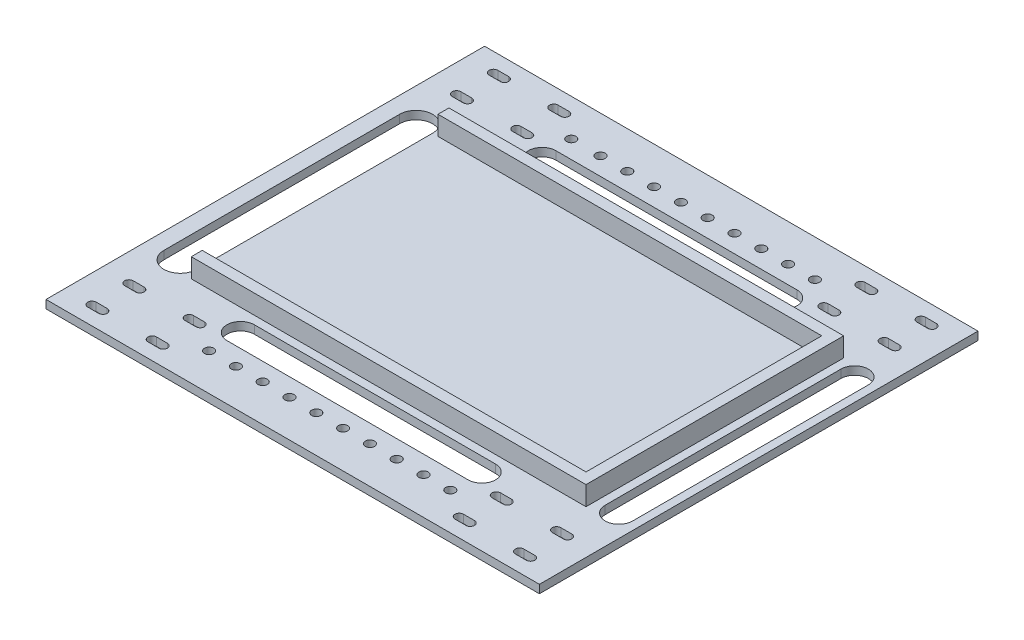
SolidWorks part; units mm, degrees
note: The reader was unsure of these and kept them because the rebuilt part matched: shared geometry of "Sketch1<3>".
ref_plane "Front Plane" through (0, 0, 0) normal (0, 0, 1) x (1, 0, 0)
ref_plane "Top Plane" through (0, 0, 0) normal (0, 1, 0) x (1, 0, 0)
ref_plane "Right Plane" through (0, 0, 0) normal (1, 0, 0) x (0, 0, -1)
sketch "Sketch1" plane through (0, 0, 0) normal (0, 1, 0) x (1, 0, 0)
  line L0 (0, -45) -> (0, 45) construction
  line L1 (-90, -80) -> (90, -80)
  line L2 (-90, -80) -> (-90, 80)
  line L3 (-90, 80) -> (90, 80)
  line L4 (90, -80) -> (90, 80)
  line L5 (-90, -80) -> (90, 80) construction
  line L6 (-90, 80) -> (90, -80) construction
  line L17 (-70, 43) -> (70, 43)
  line L18 (-70, 43) -> (-70, 47)
  line L21 (-70, 47) -> (70, 47)
  line L22 (70, 43) -> (70, 47)
  line L23 (-70, 43) -> (70, 47) construction
  line L24 (-70, 47) -> (70, 43) construction
  line L25 (-70, -47) -> (70, -47)
  line L26 (-70, -47) -> (-70, -43)
  line L27 (-70, -43) -> (70, -43)
  line L28 (70, -47) -> (70, -43)
  line L29 (-70, -47) -> (70, -43) construction
  line L30 (-70, -43) -> (70, -47) construction
  line L31 (0, 0) -> (-90, 0) construction
  line L36 (74, -47) -> (70, -47)
  line L37 (74, -47) -> (74, 47)
  line L38 (74, 47) -> (70, 47)
  line L39 (70, -47) -> (70, 47)
  line L40 (74, -47) -> (70, 47) construction
  line L41 (74, 47) -> (70, -47) construction
  line L42 (-80, -59.75) -> (-76, -59.75) construction
  line L43 (-80, -58.195) -> (-76, -58.195)
  line L44 (-80, -61.305) -> (-76, -61.305)
  line L45 (-58, -59.75) -> (-54, -59.75) construction
  line L46 (-58, -58.195) -> (-54, -58.195)
  line L47 (-58, -61.305) -> (-54, -61.305)
  line L48 (-80, -73.25) -> (-76, -73.25) construction
  line L49 (-80, -71.695) -> (-76, -71.695)
  line L50 (-80, -74.805) -> (-76, -74.805)
  line L51 (-58, -73.25) -> (-54, -73.25) construction
  line L52 (-58, -71.695) -> (-54, -71.695)
  line L53 (-58, -74.805) -> (-54, -74.805)
  line L54 (-80, 73.25) -> (-76, 73.25) construction
  line L55 (-80, 71.695) -> (-76, 71.695)
  line L56 (-80, 74.805) -> (-76, 74.805)
  line L57 (-58, 73.25) -> (-54, 73.25) construction
  line L58 (-58, 71.695) -> (-54, 71.695)
  line L59 (-58, 74.805) -> (-54, 74.805)
  line L60 (-58, 59.75) -> (-54, 59.75) construction
  line L61 (-58, 58.195) -> (-54, 58.195)
  line L62 (-58, 61.305) -> (-54, 61.305)
  line L63 (-80, 59.75) -> (-76, 59.75) construction
  line L64 (-80, 58.195) -> (-76, 58.195)
  line L65 (-80, 61.305) -> (-76, 61.305)
  line L66 (80, -73.25) -> (76, -73.25) construction
  line L67 (80, -71.695) -> (76, -71.695)
  line L68 (80, -74.805) -> (76, -74.805)
  line L69 (80, -59.75) -> (76, -59.75) construction
  line L70 (80, -58.195) -> (76, -58.195)
  line L71 (80, -61.305) -> (76, -61.305)
  line L72 (58, -59.75) -> (54, -59.75) construction
  line L73 (58, -58.195) -> (54, -58.195)
  line L74 (58, -61.305) -> (54, -61.305)
  line L75 (58, -73.25) -> (54, -73.25) construction
  line L76 (58, -71.695) -> (54, -71.695)
  line L77 (58, -74.805) -> (54, -74.805)
  line L78 (80, 59.75) -> (76, 59.75) construction
  line L79 (80, 58.195) -> (76, 58.195)
  line L80 (80, 61.305) -> (76, 61.305)
  line L81 (58, 59.75) -> (54, 59.75) construction
  line L82 (58, 58.195) -> (54, 58.195)
  line L83 (58, 61.305) -> (54, 61.305)
  line L84 (58, 73.25) -> (54, 73.25) construction
  line L85 (58, 71.695) -> (54, 71.695)
  line L86 (58, 74.805) -> (54, 74.805)
  line L87 (80, 73.25) -> (76, 73.25) construction
  line L88 (80, 71.695) -> (76, 71.695)
  line L89 (80, 74.805) -> (76, 74.805)
  line L90 (-56, 66.5) -> (56, 66.5) construction
  line L91 (-56, 73.25) -> (-56, 59.75) construction
  line L92 (56, 73.25) -> (56, 59.75) construction
  line L93 (-56, -66.5) -> (56, -66.5) construction
  line L94 (56, -73.25) -> (56, -59.75) construction
  line L95 (-56, -73.25) -> (-56, -59.75) construction
  line L96 (-78, 43) -> (-78, -43) construction
  line L97 (-78, -43) -> (-78, 43) construction
  line L98 (-84, -43) -> (-84, 43)
  line L99 (-72, -43) -> (-72, 43)
  line L100 (82, -43) -> (82, 43) construction
  line L101 (77, -43) -> (77, 43)
  line L102 (87, -43) -> (87, 43)
  line L103 (-44, 55) -> (44, 55) construction
  line L104 (-44, 60) -> (44, 60)
  line L105 (-44, 50) -> (44, 50)
  line L106 (-44, -55) -> (44, -55) construction
  line L107 (-44, -60) -> (44, -60)
  line L108 (-44, -50) -> (44, -50)
  arc A0 (-80, -58.195) -> (-80, -61.305) centre (-80, -59.75) ccw
  arc A1 (-76, -61.305) -> (-76, -58.195) centre (-76, -59.75) ccw
  arc A2 (-58, -58.195) -> (-58, -61.305) centre (-58, -59.75) ccw
  arc A3 (-54, -61.305) -> (-54, -58.195) centre (-54, -59.75) ccw
  arc A4 (-80, -71.695) -> (-80, -74.805) centre (-80, -73.25) ccw
  arc A5 (-76, -74.805) -> (-76, -71.695) centre (-76, -73.25) ccw
  arc A6 (-58, -71.695) -> (-58, -74.805) centre (-58, -73.25) ccw
  arc A7 (-54, -74.805) -> (-54, -71.695) centre (-54, -73.25) ccw
  arc A8 (-80, 71.695) -> (-80, 74.805) centre (-80, 73.25) cw
  arc A9 (-76, 74.805) -> (-76, 71.695) centre (-76, 73.25) cw
  arc A10 (-58, 71.695) -> (-58, 74.805) centre (-58, 73.25) cw
  arc A11 (-54, 74.805) -> (-54, 71.695) centre (-54, 73.25) cw
  arc A12 (-58, 58.195) -> (-58, 61.305) centre (-58, 59.75) cw
  arc A13 (-54, 61.305) -> (-54, 58.195) centre (-54, 59.75) cw
  arc A14 (-80, 58.195) -> (-80, 61.305) centre (-80, 59.75) cw
  arc A15 (-76, 61.305) -> (-76, 58.195) centre (-76, 59.75) cw
  arc A16 (80, -71.695) -> (80, -74.805) centre (80, -73.25) cw
  arc A17 (76, -74.805) -> (76, -71.695) centre (76, -73.25) cw
  arc A18 (80, -58.195) -> (80, -61.305) centre (80, -59.75) cw
  arc A19 (76, -61.305) -> (76, -58.195) centre (76, -59.75) cw
  arc A20 (58, -58.195) -> (58, -61.305) centre (58, -59.75) cw
  arc A21 (54, -61.305) -> (54, -58.195) centre (54, -59.75) cw
  arc A22 (58, -71.695) -> (58, -74.805) centre (58, -73.25) cw
  arc A23 (54, -74.805) -> (54, -71.695) centre (54, -73.25) cw
  arc A24 (80, 58.195) -> (80, 61.305) centre (80, 59.75) ccw
  arc A25 (76, 61.305) -> (76, 58.195) centre (76, 59.75) ccw
  arc A26 (58, 58.195) -> (58, 61.305) centre (58, 59.75) ccw
  arc A27 (54, 61.305) -> (54, 58.195) centre (54, 59.75) ccw
  arc A28 (58, 71.695) -> (58, 74.805) centre (58, 73.25) ccw
  arc A29 (54, 74.805) -> (54, 71.695) centre (54, 73.25) ccw
  arc A30 (80, 71.695) -> (80, 74.805) centre (80, 73.25) ccw
  arc A31 (76, 74.805) -> (76, 71.695) centre (76, 73.25) ccw
  arc A32 (-84, -43) -> (-72, -43) centre (-78, -43) ccw
  arc A33 (-72, 43) -> (-84, 43) centre (-78, 43) ccw
  arc A34 (77, -43) -> (87, -43) centre (82, -43) ccw
  arc A35 (87, 43) -> (77, 43) centre (82, 43) ccw
  arc A36 (-44, 60) -> (-44, 50) centre (-44, 55) ccw
  arc A37 (44, 50) -> (44, 60) centre (44, 55) ccw
  arc A38 (-44, -60) -> (-44, -50) centre (-44, -55) cw
  arc A39 (44, -50) -> (44, -60) centre (44, -55) cw
  point P0 (0, 0)
  point P6 (0, 45)
  point P7 (0, -45)
  point P19 (0, 0)
  point P21 (72, 0)
  point P27 (-78, -59.75)
  point P33 (-56, -59.75)
  point P40 (-78, -73.25)
  point P47 (-56, -73.25)
  point P56 (0, 66.5)
  point P59 (-78, 73.25)
  point P66 (-56, 73.25)
  point P73 (-56, 59.75)
  point P80 (-78, 59.75)
  point P87 (78, -73.25)
  point P94 (78, -59.75)
  point P101 (56, -59.75)
  point P108 (56, -73.25)
  point P115 (78, 59.75)
  point P122 (56, 59.75)
  point P129 (56, 73.25)
  point P136 (78, 73.25)
  point P142 (-44, 66.5)
  point P143 (-56, 66.5)
  point P144 (-34.2222, 66.5)
  point P148 (-24.4444, 66.5)
  point P149 (-14.6667, 66.5)
  point P150 (-4.8889, 66.5)
  point P151 (4.8889, 66.5)
  point P152 (14.6667, 66.5)
  point P153 (24.4444, 66.5)
  point P154 (34.2222, 66.5)
  point P155 (44, 66.5)
  point P157 (-4.8889, -66.5)
  point P158 (4.8889, -66.5)
  point P159 (14.6667, -66.5)
  point P160 (24.4444, -66.5)
  point P161 (34.2222, -66.5)
  point P162 (44, -66.5)
  point P167 (-14.6667, -66.5)
  point P168 (-24.4444, -66.5)
  point P169 (-34.2222, -66.5)
  point P170 (-44, -66.5)
  point P174 (-78, 0)
  point P181 (82, 0)
  point P187 (0, 55)
  point P193 (0, 0)
  point P194 (0, 0)
  point P195 (0, 0)
  point P196 (0, 58.195)
  point P197 (0, 0)
  point P200 (0, -55)
  dimension "D1" = 180
  dimension "D2" = 3.11
  dimension "D3" = 86
  dimension "D4" = 4
  dimension "D5" = 140
  dimension "D6" = 4
  dimension "D7" = 18
  dimension "D8" = 13.5
  dimension "D9" = 6.75
  dimension "D10" = 10
  dimension "D11" = 160
  dimension "D12" = 12
  dimension "D14" = 12
  dimension "D15" = 10
  dimension "D16" = 8
  dimension "D17" = 8
  dimension "D18" = 10
  dimension "D13" = 10
extrude "Boss-Extrude1" add sketch "Sketch1" along normal blind 3 contours L27 L39 L17 L18 L3 L2 L1 L26 | L17 L22 L3 L18 | L39 L28 L1 L37 L3 L22 | L37 L1 L4 L3
extrude "Boss-Extrude2" add sketch "Sketch1<3>" along normal blind 10 contours L39 L28 L1 L37 L3 L22
sketch "Sketch1<3>" plane through (0, 0, 0) normal (0, 1, 0) x (1, 0, 0) same geometry as "Sketch1"
hole_wizard "M3 Clearance Hole1" positions "Sketch2" profile "Sketch3" hole size "M3" standard "ANSI Metric"
sketch "Sketch2" plane through (0, 3, 0) normal (0, 1, 0) x (1, 0, 0)
  line L0 (-56, 66.5) -> (56, 66.5) construction
  point P0 (-44, -66.5)
  point P3 (-34.2222, -66.5)
  point P6 (-24.4444, -66.5)
  point P9 (-14.6667, -66.5)
  point P12 (-4.8889, -66.5)
  point P15 (4.8889, -66.5)
  point P18 (14.6667, -66.5)
  point P21 (24.4444, -66.5)
  point P24 (34.2222, -66.5)
  point P27 (44, -66.5)
  point P30 (44, 66.5)
  point P33 (34.2222, 66.5)
  point P36 (24.4444, 66.5)
  point P39 (14.6667, 66.5)
  point P42 (4.8889, 66.5)
  point P45 (-4.8889, 66.5)
  point P48 (-14.6667, 66.5)
  point P51 (-24.4444, 66.5)
  point P54 (-34.2222, 66.5)
  point P57 (-44.8813, 66.5)
sketch "Sketch3" plane through (-44, 3, 66.5) normal (1, 0, 0) x (0, 0, 1)
  line L0 (0, 0) -> (0, 4.0205)
  line L1 (0, 4.0205) -> (1.7, 2.999)
  line L2 (1.7, 2.999) -> (1.7, 0)
  line L5 (1.7, 0) -> (0, 0)
  line L10 (0, 4.0205) -> (-1.7, 2.999) construction
  line L11 (0, -6.35) -> (0, 107.95) construction
  dimension "Hole Dia." = 3.4
  dimension "Hole Depth" = 2.999
  dimension "Drill Angle" = 118
